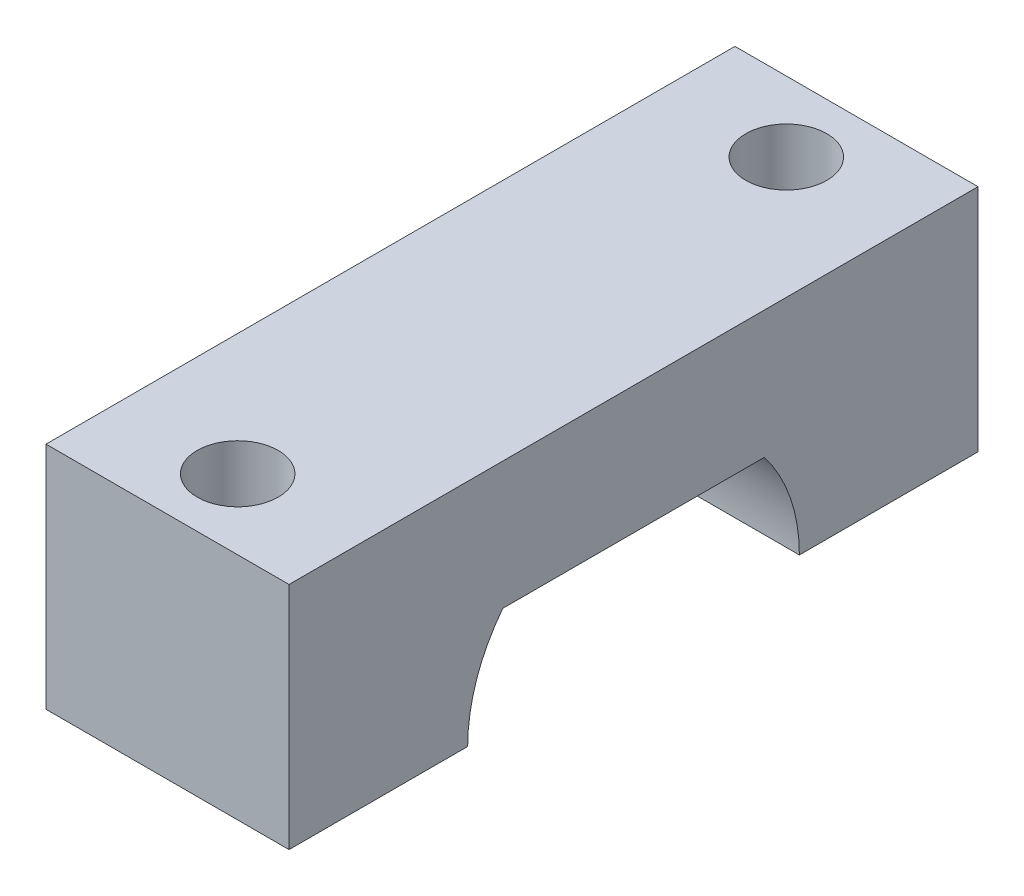
SolidWorks part; units mm, degrees
ref_plane "Front Plane" through (0, 0, 0) normal (0, 0, 1) x (1, 0, 0)
ref_plane "Top Plane" through (0, 0, 0) normal (0, 1, 0) x (1, 0, 0)
ref_plane "Right Plane" through (0, 0, 0) normal (1, 0, 0) x (0, 0, -1)
sketch "Sketch1" plane through (0, 0, 0) normal (1, 0, 0) x (0, 0, -1)
  line L0 (-6.5, 0) -> (-13.5, 0)
  line L1 (13.5, 9) -> (-13.5, 9)
  line L2 (13.5, 9) -> (13.5, 0)
  line L3 (13.5, 0) -> (6.5, 0)
  line L4 (-13.5, 9) -> (-13.5, 0)
  line L5 (-5.1235, 4) -> (5.1235, 4)
  arc A0 (6.5, 0) -> (5.1235, 4) centre (0, 0) ccw
  arc A1 (-5.1235, 4) -> (-6.5, 0) centre (0, 0) ccw
  dimension "D1" = 13
  dimension "D2" = 0
  dimension "D3" = 27
  dimension "D4" = 13.5
  dimension "D5" = 9
  dimension "D6" = 4
extrude "Boss-Extrude1" add sketch "Sketch1" along normal blind 9.525
sketch "Sketch2" plane through (0, 9, 0) normal (0, 1, 0) x (1, 0, 0)
  line L0 (9.525, -13.5) -> (0, -13.5) construction
  line L1 (9.525, 13.5) -> (9.525, -13.5) construction
  line L2 (9.525, 13.5) -> (0, 13.5) construction
  circle A0 centre (4.7625, -10.75) radius 1.5875
  circle A1 centre (4.7625, 10.75) radius 1.5875
  dimension "D1" = 3.175
  dimension "D4" = 3.175
  dimension "D2" = 2.75
  dimension "D3" = 4.7625
  dimension "D5" = 2.75
  dimension "D6" = 4.7625
extrude "Cut-Extrude1" cut sketch "Sketch2" against normal through all
equation "\"D4@Sketch1\"=\"D3@Sketch1\"/2"
equation "\"D5@Sketch2\"=\"D2@Sketch2\""
equation "\"D4@Sketch2\"=\"D1@Sketch2\""
equation "\"D6@Sketch2\"=\"D3@Sketch2\""
